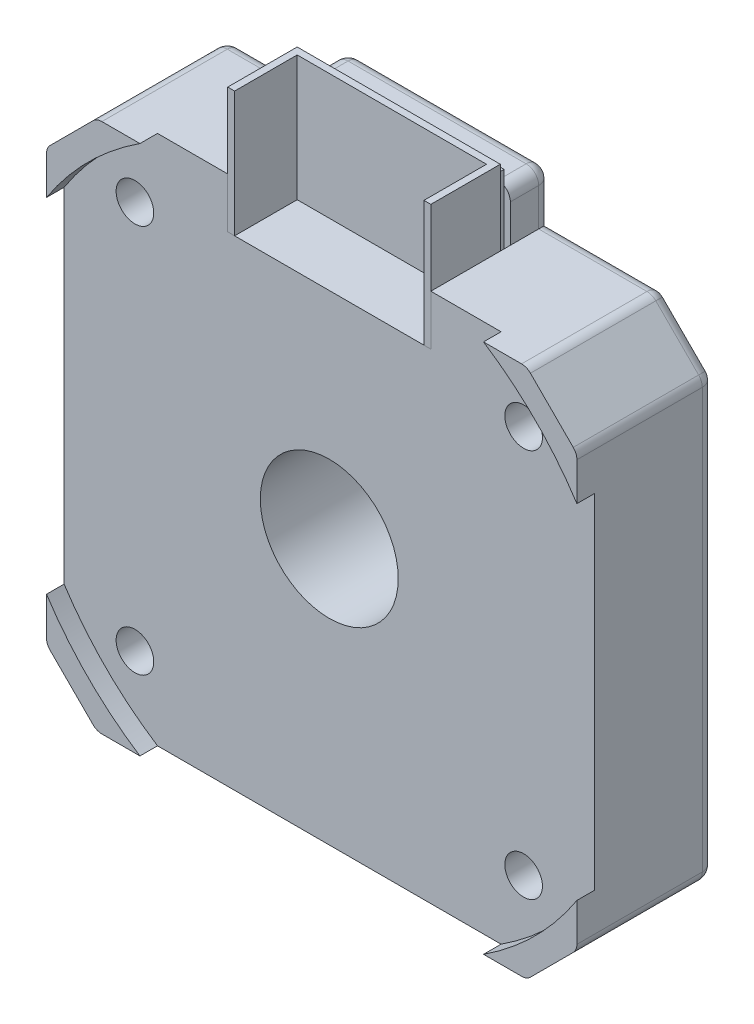
SolidWorks part; units mm, degrees
material "Acero aleado"
ref_plane "Alzado" through (0, 0, 0) normal (0, 0, 1) x (1, 0, 0)
ref_plane "Planta" through (0, 0, 0) normal (0, 1, 0) x (1, 0, 0)
ref_plane "Vista lateral" through (0, 0, 0) normal (1, 0, 0) x (0, 0, -1)
sketch "Croquis1" plane through (0, 0, 0) normal (0, 0, 1) x (1, 0, 0)
  line L0 (-17.15, 21.15) -> (-21.15, 17.15)
  line L1 (-17.15, 21.15) -> (17.15, 21.15)
  line L2 (-21.15, 17.15) -> (-21.15, -17.15)
  line L3 (-17.15, -21.15) -> (17.15, -21.15)
  line L4 (21.15, 17.15) -> (21.15, -17.15)
  line L5 (-21.15, 21.15) -> (21.15, -21.15) construction
  line L6 (-21.15, -21.15) -> (21.15, 21.15) construction
  line L7 (-21.15, -17.15) -> (-17.15, -21.15)
  line L8 (17.15, -21.15) -> (21.15, -17.15)
  line L9 (17.15, 21.15) -> (21.15, 17.15)
  point P0 (0, 0)
  dimension "D1" = 42.3
  dimension "D2" = 42.3
extrude "Saliente-Extruir4" add sketch "Croquis1" along normal blind 9.6
sketch "Croquis4" plane through (0, 0, 9.6) normal (0, 0, 1) x (1, 0, 0)
  line L0 (-21.15, 14.15) -> (-14.15, 21.15)
  line L1 (-14.15, 21.15) -> (14.15, 21.15)
  line L2 (-21.15, 14.15) -> (-21.15, -14.15)
  line L3 (-14.15, -21.15) -> (14.15, -21.15)
  line L4 (21.15, 14.15) -> (21.15, -14.15)
  line L5 (-21.15, 21.15) -> (21.15, -21.15) construction
  line L6 (-21.15, -21.15) -> (21.15, 21.15) construction
  line L7 (-21.15, -14.15) -> (-14.15, -21.15)
  line L8 (14.15, -21.15) -> (21.15, -14.15)
  line L9 (14.15, 21.15) -> (21.15, 14.15)
  point P0 (0, 0)
  dimension "D1" = 42.3
  dimension "D2" = 42.3
extrude "Cortar-Extruir1" [suppressed] cut sketch "Croquis4" against normal blind 2
sketch "Croquis5" plane through (0, 0, 0) normal (0, 0, -1) x (-1, 0, 0)
  circle A0 centre (-15.5, 15.5) radius 1.5
  circle A1 centre (15.5, 15.5) radius 1.5
  circle A2 centre (15.5, -15.5) radius 1.5
  circle A3 centre (-15.5, -15.5) radius 1.5
  point P12 (0, 0)
  dimension "D1" = 3
  dimension "D2" = 15.5
  dimension "D3" = 15.5
  dimension "D5" = 31
  dimension "D6" = 15.5
  dimension "D4" = 4
extrude "Cortar-Extruir2" cut sketch "Croquis5" against normal blind 22
sketch "Croquis6" plane through (0, 0, 0) normal (0, 0, -1) x (-1, 0, 0)
  circle A0 centre (0, 0) radius 4.3
  dimension "D1" = 8.6
extrude "Cortar-Extruir3" cut sketch "Croquis6" against normal blind 1
fillet "Redondeo1" radius 1 8 edges at (-19.15, 19.15, 0) (-19.15, -19.15, 0) (-21.15, 0, 0) (0, -21.15, 0) (19.15, -19.15, 0) (21.15, 0, 0) (19.15, 19.15, 0) (0, 21.15, 0)
sketch "Croquis7" plane through (0, 0, 0) normal (0, 0, -1) x (-1, 0, 0)
  circle A0 centre (-15.5, 15.5) radius 3.1
  circle A1 centre (15.5, 15.5) radius 3.1
  circle A2 centre (15.5, -15.5) radius 3.1
  circle A3 centre (-15.5, -15.5) radius 3.1
  point P11 (0, 0)
  dimension "D1" = 6.2
  dimension "D3" = 15.5
  dimension "D4" = 15.5
  dimension "D2" = 4
extrude "Cortar-Extruir4" cut sketch "Croquis7" against normal blind 3
fillet "Redondeo2" radius 0.5 7 edges at (12.4, -15.5, 0) (-18.6, -15.5, 3) (-18.6, -15.5, 0) (-18.6, 15.5, 3) (-18.6, 15.5, 0) (12.4, 15.5, 3) (12.4, 15.5, 0)
sketch "Croquis8" plane through (0, 0, 1) normal (0, 0, -1) x (-1, 0, 0)
  circle A0 centre (0, 0) radius 5.5
  dimension "D1" = 11
extrude "Cortar-Extruir5" cut sketch "Croquis8" against normal blind 22
sketch "Эскиз1" [suppressed] plane through (0, 0, 10) normal (0, 0, 1) x (1, 0, 0)
  line L1 (-21.15, 21.15) -> (21.15, 21.15)
  line L2 (-21.15, 21.15) -> (-21.15, -21.15)
  line L3 (-21.15, -21.15) -> (21.15, -21.15)
  line L4 (21.15, 21.15) -> (21.15, -21.15)
extrude "Вырез-Вытянуть1" [suppressed] cut sketch "Эскиз1" along normal up to vertex
sketch "Эскиз2" plane through (0, 21.15, 0) normal (0, 1, 0) x (1, 0, 0)
  line L0 (-16.7358, 0) -> (16.7358, 0) construction
  line L1 (-8.1, 0) -> (8.1, 0)
  line L2 (-8.1, 0) -> (-8.1, -3.26)
  line L3 (-8.1, -3.26) -> (8.1, -3.26)
  line L4 (8.1, 0) -> (8.1, -3.26)
  point P6 (0, -3.26)
  dimension "D1" = 16.2
  dimension "D2" = 3.26
extrude "Бобышка-Вытянуть1" add sketch "Эскиз2" along normal blind 4 and the other way blind 1
fillet "Скругление1" radius 1 3 edges at (8.1, 22.65, 0) (0, 25.15, 0) (-8.1, 22.65, 0)
fillet "Скругление2" radius 1 4 edges at (7.8071, 24.8571, 0.2929) (-7.8071, 24.8571, 0.2929) (8.1, 25.15, 2.13) (-8.1, 25.15, 2.13)
sketch "Эскиз3" plane through (0, 21.15, 0) normal (0, 1, 0) x (1, 0, 0)
  line L0 (17.15, -9.6) -> (-17.15, -9.6) construction
  line L1 (-8.1, -3.26) -> (8.1, -3.26)
  line L2 (-8.1, -3.26) -> (-8.1, -9.6)
  line L3 (-8.1, -9.6) -> (8.1, -9.6)
  line L4 (8.1, -3.26) -> (8.1, -9.6)
extrude "Вырез-Вытянуть2" cut sketch "Эскиз3" against normal blind 4
sketch "Эскиз4" plane through (0, 17.15, 0) normal (0, 1, 0) x (1, 0, 0)
  line L0 (-8.1, -3.26) -> (-7.1, -3.26) construction
  line L1 (-7.6, -3.26) -> (7.6, -3.26)
  line L2 (-7.6, -3.26) -> (-7.6, -4.06)
  line L3 (-7.6, -4.06) -> (7.6, -4.06)
  line L4 (7.6, -3.26) -> (7.6, -4.06)
  line L5 (7.1, -3.26) -> (8.1, -3.26) construction
  dimension "D1" = 0.8
extrude "Бобышка-Вытянуть2" add sketch "Эскиз4" along normal offset from surface (9 mm away) 1 separate body up to face at (0, 25.15, 2.13) offset beyond the face yes
sketch "Эскиз5" plane through (0, 17.15, 0) normal (0, 1, 0) x (1, 0, 0)
  line L0 (-8.1, -9.6) -> (-8.1, -4.06)
  line L1 (-8.1, -4.06) -> (8.1, -4.06)
  line L2 (8.1, -4.06) -> (8.1, -9.6)
  line L3 (8.1, -9.6) -> (7.55, -9.6)
  line L4 (-8.1, -9.6) -> (8.1, -9.6) construction
  line L5 (7.55, -9.6) -> (7.55, -4.61)
  line L6 (7.55, -4.61) -> (-7.55, -4.61)
  line L7 (-7.55, -4.61) -> (-7.55, -9.6)
  line L8 (-7.55, -9.6) -> (-8.1, -9.6)
  dimension "D1" = 0.55
  dimension "D2" = 0.55
  dimension "D3" = 0.55
extrude "Бобышка-Вытянуть3" add sketch "Эскиз5" along normal offset from surface (10 mm away) 1 separate body up to face at (0, 26.15, 3.66) offset beyond the face yes
fillet "Скругление3" radius 1 16 edges at (-20.8571, -17.0287, 0.2929) (-17.0287, -20.8571, 0.2929) (17.0287, -20.8571, 0.2929) (20.8571, -17.0287, 0.2929) (-20.8571, 17.0287, 0.2929) (-17.0287, 20.8571, 0.2929) (20.8571, 17.0287, 0.2929) (17.0287, 20.8571, 0.2929) (-21.15, -17.15, 5.3) (-17.15, -21.15, 5.3) (17.15, -21.15, 5.3) (21.15, -17.15, 5.3) (-21.15, 17.15, 5.3) (-17.15, 21.15, 5.3) (21.15, 17.15, 5.3) (17.15, 21.15, 5.3)
sketch "Эскиз6" plane through (0, 0, 9.6) normal (0, 0, 1) x (1, 0, 0)
  line L0 (-21.15, -13.701) -> (-21.15, -16.7358)
  line L1 (21.15, 13.701) -> (21.15, 16.7358)
  line L2 (13.701, -21.15) -> (16.7358, -21.15)
  line L12 (-21.15, 16.7358) -> (-21.15, -16.7358)
  line L13 (-20.8571, -17.4429) -> (-17.4429, -20.8571)
  line L14 (-16.7358, -21.15) -> (16.7358, -21.15)
  line L15 (17.4429, -20.8571) -> (20.8571, -17.4429)
  line L16 (21.15, -16.7358) -> (21.15, 16.7358)
  line L17 (20.8571, 17.4429) -> (17.4429, 20.8571)
  line L18 (16.7358, 21.15) -> (8.1, 21.15)
  line L19 (8.1, 21.15) -> (8.1, 17.15)
  line L20 (8.1, 17.15) -> (-8.1, 17.15)
  line L21 (-8.1, 17.15) -> (-8.1, 21.15)
  line L22 (-8.1, 21.15) -> (-16.7358, 21.15)
  line L23 (-17.4429, 20.8571) -> (-20.8571, 17.4429)
  line L24 (-21.15, 16.7358) -> (-21.15, 13.701)
  line L25 (-20.8571, -17.4429) -> (-17.4429, -20.8571)
  line L26 (-16.7358, -21.15) -> (-13.701, -21.15)
  line L27 (17.4429, -20.8571) -> (20.8571, -17.4429)
  line L28 (21.15, -16.7358) -> (21.15, -13.701)
  line L29 (20.8571, 17.4429) -> (17.4429, 20.8571)
  line L30 (16.7358, 21.15) -> (13.701, 21.15)
  line L34 (-13.701, 21.15) -> (-16.7358, 21.15)
  line L35 (-17.4429, 20.8571) -> (-20.8571, 17.4429)
  arc A0 (13.701, -21.15) -> (21.15, -13.701) centre (0, 0) ccw
  arc A1 (-21.15, -13.701) -> (-13.701, -21.15) centre (0, 0) ccw
  arc A2 (-13.701, 21.15) -> (-21.15, 13.701) centre (0, 0) ccw
  arc A3 (21.15, 13.701) -> (13.701, 21.15) centre (0, 0) ccw
  arc A10 (-21.15, -16.7358) -> (-20.8571, -17.4429) centre (-20.15, -16.7358) ccw
  arc A11 (-17.4429, -20.8571) -> (-16.7358, -21.15) centre (-16.7358, -20.15) ccw
  arc A12 (16.7358, -21.15) -> (17.4429, -20.8571) centre (16.7358, -20.15) ccw
  arc A13 (20.8571, -17.4429) -> (21.15, -16.7358) centre (20.15, -16.7358) ccw
  arc A14 (21.15, 16.7358) -> (20.8571, 17.4429) centre (20.15, 16.7358) ccw
  arc A15 (17.4429, 20.8571) -> (16.7358, 21.15) centre (16.7358, 20.15) ccw
  arc A16 (-16.7358, 21.15) -> (-17.4429, 20.8571) centre (-16.7358, 20.15) ccw
  arc A17 (-20.8571, 17.4429) -> (-21.15, 16.7358) centre (-20.15, 16.7358) ccw
  arc A18 (-21.15, -16.7358) -> (-20.8571, -17.4429) centre (-20.15, -16.7358) ccw
  arc A19 (-17.4429, -20.8571) -> (-16.7358, -21.15) centre (-16.7358, -20.15) ccw
  arc A20 (16.7358, -21.15) -> (17.4429, -20.8571) centre (16.7358, -20.15) ccw
  arc A21 (20.8571, -17.4429) -> (21.15, -16.7358) centre (20.15, -16.7358) ccw
  arc A22 (21.15, 16.7358) -> (20.8571, 17.4429) centre (20.15, 16.7358) ccw
  arc A23 (17.4429, 20.8571) -> (16.7358, 21.15) centre (16.7358, 20.15) ccw
  arc A24 (-16.7358, 21.15) -> (-17.4429, 20.8571) centre (-16.7358, 20.15) ccw
  arc A25 (-20.8571, 17.4429) -> (-21.15, 16.7358) centre (-20.15, 16.7358) ccw
  dimension "D1" = 50.4
  dimension "D2" = 0
extrude "Бобышка-Вытянуть4" add sketch "Эскиз6" along normal offset from surface (1.4 mm away) 11 up to face at (19.1, -15.5, 0)
